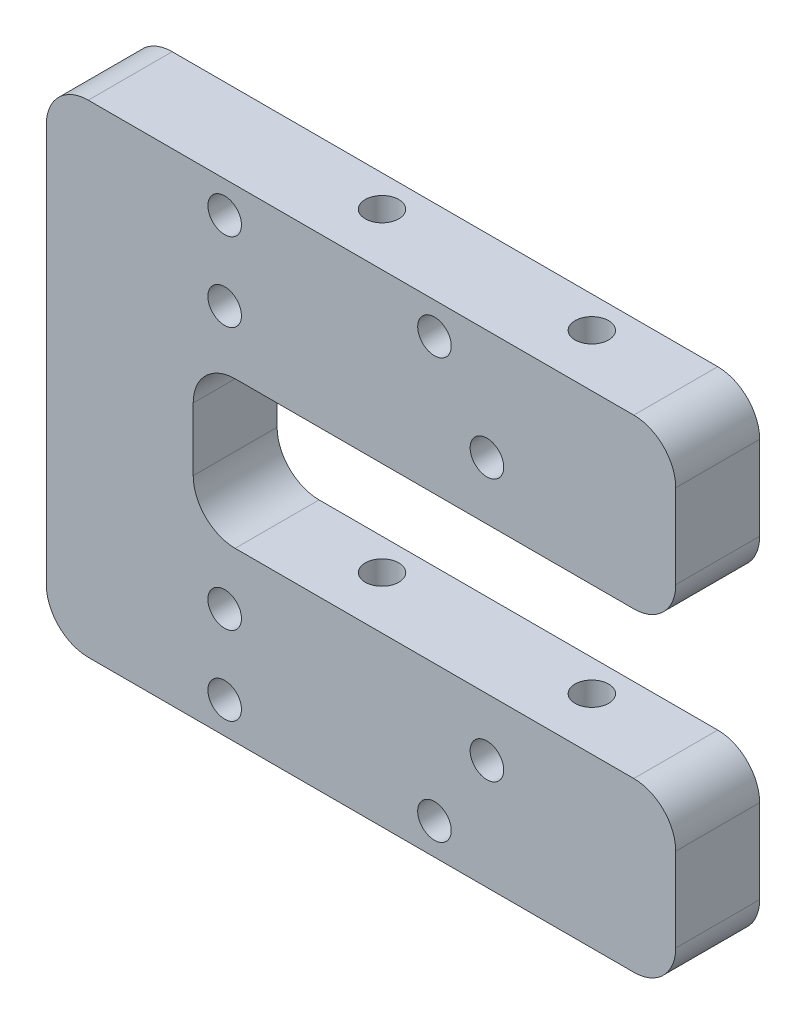
SolidWorks part; units mm, degrees
material "3003 合金"
ref_plane "前视基准面" through (0, 0, 0) normal (0, 0, 1) x (1, 0, 0)
ref_plane "上视基准面" through (0, 0, 0) normal (0, 1, 0) x (1, 0, 0)
ref_plane "右视基准面" through (0, 0, 0) normal (1, 0, 0) x (0, 0, -1)
other "Configuration Table"
sketch "草图1" plane through (0, 0, 0) normal (0, 0, 1) x (1, 0, 0)
  line L0 (0, 23) -> (95.8228, 23) construction
  line L1 (0, 0) -> (60, 0)
  line L2 (0, 0) -> (0, 46)
  line L3 (0, 46) -> (60, 46)
  line L4 (60, 0) -> (60, 16)
  line L5 (14, 16) -> (60, 16)
  line L7 (14, 16) -> (14, 30)
  line L8 (14, 30) -> (60, 30)
  line L10 (60, 30) -> (60, 46)
  line L11 (14, 16) -> (60, 16)
  circle A0 centre (17, 35.5) radius 1.6
  circle A1 centre (42, 35.5) radius 1.6
  circle A2 centre (42, 10.5) radius 1.6
  circle A3 centre (17, 10.5) radius 1.6
  dimension "D6" = 25
  dimension "3.2" = 3.2
  dimension "D7" = 25
  dimension "D8" = 17
  dimension "D1" = 60
  dimension "D2" = 46
  dimension "D3" = 46
  dimension "D4" = 7
  dimension "D5" = 2
extrude "凸台-拉伸1" add sketch "草图1" along normal blind 8 contours L2 L0 L7 L8 L10 L3 A0 A1 | L0 L2 L1 L4 L5 L7 A2 A3 region at (27.8444, 36.9569, 0) region at (27.8444, 9.0431, 0)
fillet "圆角1" radius 4 8 edges at (0, 46, 4) (60, 46, 4) (60, 30, 4) (14, 30, 4) (14, 16, 4) (60, 16, 4) (0, 0, 4) (60, 0, 4)
sketch "草图2" plane through (0, 0, 8) normal (0, 0, 1) x (1, 0, 0)
  line L0 (0, 4) -> (0, 42) construction
  line L1 (0, 23) -> (82.9703, 23) construction
  circle A0 centre (17, 3) radius 1.6
  circle A2 centre (37, 3) radius 1.6
  circle A3 centre (37, 43) radius 1.6
  circle A4 centre (17, 43) radius 1.6
  dimension "D1" = 3.2
  dimension "D2" = 17
  dimension "D4" = 40
  dimension "D5" = 20
  dimension "D3" = 2
extrude "切除-拉伸1" cut sketch "草图2" against normal blind 10
sketch "草图3" plane through (0, 46, 0) normal (0, 1, 0) x (1, 0, 0)
  line L0 (0, -8) -> (0, 0) construction
  line L1 (4, 0) -> (56, 0) construction
  circle A0 centre (27, -3) radius 1.6
  circle A1 centre (47, -3) radius 1.6
  point P8 (30, 0)
  dimension "D1" = 3.2
  dimension "D4" = 20
  dimension "D5" = 3
  dimension "D2" = 27
  dimension "D3" = 2
extrude "切除-拉伸2" cut sketch "草图3" against normal blind 67
